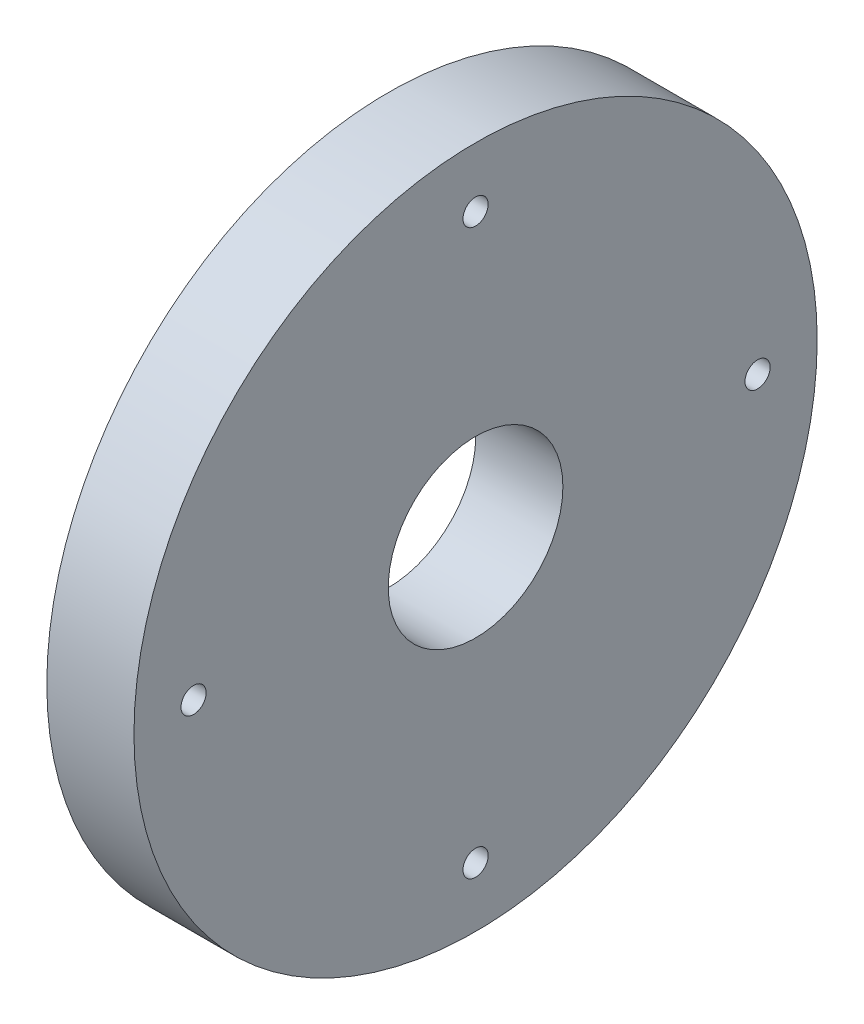
SolidWorks part; units mm, degrees
ref_plane "Front Plane" through (0, 0, 0) normal (0, 0, 1) x (1, 0, 0)
ref_plane "Top Plane" through (0, 0, 0) normal (0, 1, 0) x (1, 0, 0)
ref_plane "Right Plane" through (0, 0, 0) normal (1, 0, 0) x (0, 0, -1)
sketch "Sketch1" plane through (0, 0, 0) normal (1, 0, 0) x (0, 0, -1)
  circle A0 centre (0, 0) radius 6.3627
  circle A1 centre (0, 0) radius 24.892
extrude "Boss-Extrude1" add sketch "Sketch1" along normal blind 3.175 and the other way blind 3.175
sketch "Sketch2" plane through (3.175, 0, 0) normal (1, 0, 0) x (0, 0, -1)
  circle A0 centre (0, 20.5468) radius 0.9164
extrude "Cut-Extrude1" cut sketch "Sketch2" against normal through all both and the other way through all
pattern_circular "CirPattern1" count 4 over 360 about axis through (3.175, 0, 0) along (1, 0, 0) of "Cut-Extrude1"
sketch "Sketch3" plane through (-3.175, 0, 0) normal (-1, 0, 0) x (0, 0, 1)
  circle A0 centre (0, 20.5468) radius 3.175
extrude "Cut-Extrude2" [suppressed] cut sketch "Sketch3" against normal blind 3.175
